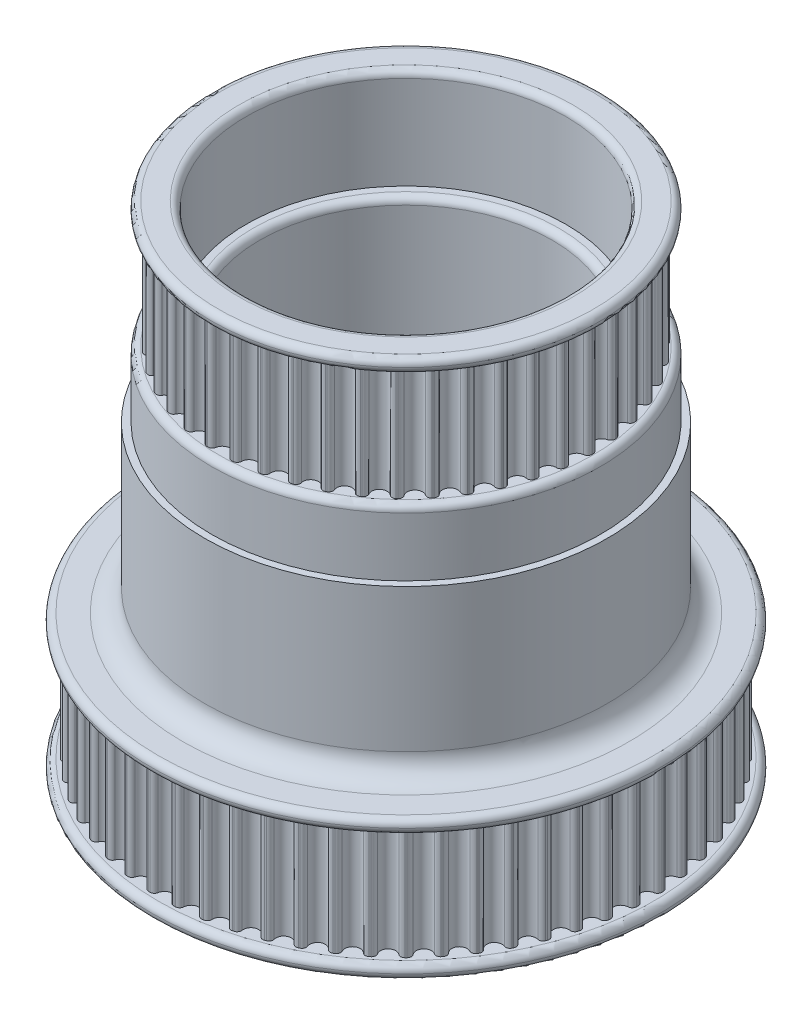
SolidWorks part; units mm, degrees
ref_plane "Front Plane" through (0, 0, 0) normal (0, 0, 1) x (1, 0, 0)
ref_plane "Top Plane" through (0, 0, 0) normal (0, 1, 0) x (1, 0, 0)
ref_plane "Right Plane" through (0, 0, 0) normal (1, 0, 0) x (0, 0, -1)
sketch "PulleyOffsets" plane through (0, 0, 0) normal (1, 0, 0) x (0, 0, -1)
  line L0 (20.6375, 0) -> (-20.6375, 0) construction
  line L1 (20.6375, 41.275) -> (-20.6375, 41.275) construction
  line L2 (0, 0) -> (0, 41.275) construction
  point P7 (0, 0)
  dimension "D1" = 41.275
ref_axis "Axis1" through (0, 34.9332, 0) along (0, -1, 0)
ref_plane "Big Pulley Plane" through (0, 0, 0) normal (0, 1, 0) x (1, 0, 0)
ref_plane "Small Pulley Plane" through (0, 41.275, 0) normal (0, 1, 0) x (1, 0, 0)
sketch "Sketch1" plane through (0, 0, 0) normal (0, 1, 0) x (1, 0, 0)
  line L0 (0, 0) -> (0, 28.2667) construction
  line L1 (0, 0) -> (2.9202, 27.7837) construction
  circle A0 centre (0, 0) radius 28.2667 construction
  circle A1 centre (0, 0) radius 27.0467 construction
  circle A2 centre (0, 27.9367) radius 0.89 construction
  circle A5 centre (2.9202, 27.7837) radius 0.89 construction
  arc A6 (0, 27.0467) -> (0.8804, 27.8061) centre (0, 27.9367) ccw
  arc A7 (0.8804, 27.8061) -> (1.3997, 28.2321) centre (1.3749, 27.7327) cw
  arc A8 (1.559, 28.2237) -> (2.031, 27.7458) centre (1.5314, 27.7245) cw
  arc A9 (2.8272, 26.8986) -> (2.031, 27.7458) centre (2.9202, 27.7837) cw
  arc A10 (1.3997, 28.2321) -> (1.559, 28.2237) centre (0, 0) cw
  arc A11 (0, 27.0467) -> (2.8272, 26.8986) centre (0, 0) ccw
  dimension "D1" = 56.5335
  dimension "D3" = 1.78
  dimension "D4" = 0.5
  dimension "D2" = 1.22
  dimension "D5" = 6
extrude "Boss-Extrude1" add sketch "Sketch1" along normal mid plane 13 contours A6 A11 A9 A8 A7 region at (0.001, 0, -0.0192)
pattern_circular "CirPattern1" count 60 over 360 about axis through (0, 34.9332, 0) along (0, -1, 0) of "Boss-Extrude1"
sketch "Sketch2" plane through (0, 0, 0) normal (1, 0, 0) x (0, 0, -1)
  line L10 (0, 6.5) -> (29.4415, 6.5) construction
  line L11 (0, 6.5) -> (0, 8.0875) construction
  line L12 (0, 8.0875) -> (29.4415, 8.0875) construction
  line L15 (29.4415, 6.5) -> (29.4415, 8.0875) construction
  line L20 (0, 34.9332) -> (0, -6.9932) construction
  line L22 (29.4415, 8.0875) -> (0, 8.0875)
  line L23 (29.4415, 8.0875) -> (29.4415, 6.5)
  line L24 (29.4415, 6.5) -> (0, 6.5)
  line L25 (0, 8.0875) -> (0, 6.5)
  dimension "D1" = 1.5875
  dimension "D2" = 29.4415
  dimension "D3" = 6.5
revolve "Revolve3" add sketch "Sketch2" angle 360 about axis through (0, 34.9332, 0) along (0, -1, 0) region at (0, 7.2937, -14.7207)
mirror "Mirror1" about plane through (0, 0, 0) normal (0, 1, 0) of "Revolve3"
sketch "Sketch6" plane through (0, 0, 0) normal (0, 1, 0) x (1, 0, 0)
  line L0 (0, 0) -> (0, 21.582) construction
  line L1 (0, 0) -> (2.8938, 21.0541) construction
  circle A0 centre (0, 0) radius 21.582 construction
  circle A1 centre (0, 0) radius 20.362 construction
  circle A2 centre (0, 21.252) radius 0.89 construction
  circle A5 centre (2.8938, 21.0541) radius 0.89 construction
  arc A6 (0, 20.362) -> (0.8793, 21.1145) centre (0, 21.252) ccw
  arc A7 (0.8793, 21.1145) -> (1.4059, 21.5362) centre (1.3733, 21.0373) cw
  arc A8 (1.5397, 21.527) -> (2.004, 21.0376) centre (1.5041, 21.0283) cw
  arc A9 (2.7726, 20.1724) -> (2.004, 21.0376) centre (2.8938, 21.0541) cw
  arc A10 (1.4059, 21.5362) -> (1.5397, 21.527) centre (0, 0) cw construction
  arc A11 (0, 20.362) -> (2.7726, 20.1724) centre (0, 0) ccw
  arc A12 (1.4059, 21.5362) -> (1.5397, 21.527) centre (0, 0) cw
  dimension "D3" = 1.78
  dimension "D4" = 0.5
  dimension "D2" = 1.22
  dimension "D1" = 43.1641
  dimension "D5" = 7.826
extrude "Boss-Extrude2" add sketch "Sketch6" along normal mid plane 13 from surface contours A6 A11 A9 A8 A7 region at (0.0017, 0, -0.025) starting at plane "Small Pulley Plane"
pattern_circular "CirPattern2" count 46 over 360 about axis through (0, 34.9332, 0) along (0, -1, 0) of "Boss-Extrude2"
sketch "Sketch9" plane through (0, 0, 0) normal (1, 0, 0) x (0, 0, -1)
  line L1 (0, 34.775) -> (22.7568, 34.775)
  line L2 (0, 34.775) -> (0, 33.1875)
  line L3 (0, 33.1875) -> (22.7568, 33.1875)
  line L4 (22.7568, 34.775) -> (22.7568, 33.1875)
  line L6 (0, 47.775) -> (22.7568, 47.775)
  line L7 (0, 47.775) -> (0, 49.3625)
  line L8 (0, 49.3625) -> (22.7568, 49.3625)
  line L9 (22.7568, 47.775) -> (22.7568, 49.3625)
  line L10 (29.4415, 8.0875) -> (29.4415, 6.5) construction
  line L11 (0, 34.9332) -> (0, -6.9932) construction
  line L12 (21.1145, 47.775) -> (20.362, 47.775) construction
  line L13 (20.1641, 34.775) -> (21.0376, 34.775) construction
  dimension "D1" = 22.7568
revolve "Revolve4" add sketch "Sketch9" angle 360 about axis through (0, 34.9332, 0) along (0, -1, 0)
sketch "Sketch10" plane through (0, -8.0875, 0) normal (0, -1, 0) x (1, 0, 0)
  circle A0 centre (0, 0) radius 18.5
  dimension "D1" = 37
extrude "Cut-Extrude1" cut sketch "Sketch10" against normal through all
sketch "Sketch11" plane through (0, 49.3625, 0) normal (0, 1, 0) x (1, 0, 0)
  circle A0 centre (0, 0) radius 22.5
  dimension "D1" = 45
extrude "Cut-Extrude2" cut sketch "Sketch11" against normal up to surface (16.175 mm away) flip side to cut up to face at (0, 33.1875, 18.5)
sketch "Sketch12" plane through (0, 0, 0) normal (0, 0, 1) x (1, 0, 0)
  line L0 (29.4415, 8.0875) -> (-29.4415, 8.0875) construction
  line L1 (18.5, 33.1875) -> (22.5, 33.1875)
  line L2 (18.5, 33.1875) -> (18.5, 8.0875) construction
  line L3 (18.5, 8.0875) -> (22.5, 8.0875)
  line L4 (22.5, 33.1875) -> (22.5, 8.0875) construction
  line L5 (22.5, 33.1875) -> (22.5, 34.775) construction
  line L6 (22.5, 27.1875) -> (22.5, 33.1875)
  line L7 (22.5, 27.1875) -> (23.2938, 27.1875)
  line L8 (22.5, 27.1875) -> (22.5, 8.0875) construction
  line L9 (22.5, 8.0875) -> (23.2938, 8.0875)
  line L10 (23.2938, 27.1875) -> (23.2938, 8.0875)
  line L11 (18.5, -8.0875) -> (18.5, 8.0875) construction
  line L12 (18.5, -1.0875) -> (16.9125, -1.0875)
  line L13 (18.5, -1.0875) -> (18.5, 37.775) construction
  line L14 (18.5, 37.775) -> (16.9125, 37.775)
  line L15 (16.9125, -1.0875) -> (16.9125, 37.775)
  line L16 (-29.4415, -8.0875) -> (29.4415, -8.0875) construction
  line L18 (18.5, -1.0875) -> (18.5, 8.0875)
  line L19 (18.5, 33.1875) -> (18.5, 37.775)
  line L20 (32.3856, 41.275) -> (-32.3856, 41.275) construction
  dimension "D1" = 6
  dimension "D2" = 0.7937
  dimension "D3" = 7
  dimension "D4" = 3.5
  dimension "D5" = 1.5875
revolve "Revolve5" add sketch "Sketch12" angle 360 about axis through (0, 34.9332, 0) along (0, -1, 0)
fillet "Fillet1" radius 2.54 1 edges at (0, 8.0875, -23.2938)
fillet "Fillet2" radius 0.7937 11 edges at (0, 37.775, 16.9125) (0, 49.3625, -18.5) (0, -8.0875, -18.5) (0, -1.0875, 16.9125) (0, -8.0875, 29.4415) (0, 8.0875, 29.4415) (0, 49.3625, 22.5) (0, 47.775, 22.5) (0, 34.775, -22.5) (0, 6.5, 29.4415) (0, -6.5, 29.4415)
equation "\"TEETH_NUM\"= 60"
equation "\"TOOTH_PITCH\"= 3mm"
equation "\"PITCH_LINE_OFFSET\"= .015in"
equation "\"DIAMETER_PER_GROOVE\"= \"OUTSIDE_DIAMETER\" / \"TEETH_NUM\" * 1in"
equation "\"PITCH_DIAMETER\"= ( ( \"TEETH_NUM\" * 3 - 1.31 ) / 3.1415 + .415 ) * 1mm"
equation "\"OUTSIDE_DIAMETER\"= \"PITCH_DIAMETER\" - \"PITCH_LINE_OFFSET\" * 2"
equation "\"D1@Sketch1\"=\"OUTSIDE_DIAMETER\""
equation "\"TOOTH_HEIGHT\"= 1.22mm"
equation "\"D2@Sketch1\"=\"TOOTH_HEIGHT\""
equation "\"TOOTH_DIAMETER\"= 1.78mm"
equation "\"INTERNAL_RADIUS\"= .5mm"
equation "\"D3@Sketch1\"=\"TOOTH_DIAMETER\""
equation "\"D5@Sketch1\"=360 / \"TEETH_NUM\""
equation "\"D4@Sketch1\"=\"INTERNAL_RADIUS\""
equation "\"D1@CirPattern1\"=\"TEETH_NUM\""
equation "\"BELT_GAP\"= 13mm"
equation "\"D2@Sketch2\"=\"PITCH_DIAMETER\"/2+1/32"
equation "\"D3@Sketch2\"=\"BELT_GAP\"/2"
equation "\"2_TEETH_NUM\"= 46"
equation "\"2_PITCH_DIAMETER\"= ( ( \"2_TEETH_NUM\" * 3 - 1.31 ) / 3.1415 + .415 ) * 1mm"
equation "\"2_OUTSIDE_DIAMETER\"= \"2_PITCH_DIAMETER\" - \"PITCH_LINE_OFFSET\" * 2"
equation "\"2_DIAMETER_PER_GROOVE\"= \"2_OUTSIDE_DIAMETER\" / \"2_TEETH_NUM\" * 1in"
equation "\"D5@Sketch6\"=360/\"2_TEETH_NUM\""
equation "\"D1@Sketch6\"=\"2_OUTSIDE_DIAMETER\""
equation "\"D2@Sketch6\"=\"TOOTH_HEIGHT\""
equation "\"D3@Sketch6\"=\"TOOTH_DIAMETER\""
equation "\"D4@Sketch6\"=\"INTERNAL_RADIUS\""
equation "\"2_BELT_GAP\"= 13mm"
equation "\"D1@CirPattern2\"=\"2_TEETH_NUM\""
equation "\"D1@Boss-Extrude2\"=\"2_BELT_GAP\""
equation "\"Pulley_OffSets\"= 1.625"
equation "\"D1@PulleyOffsets\" = \"Pulley_OffSets\""
equation "\"D1@Boss-Extrude1\"=\"BELT_GAP\""
equation "\"D1@Sketch9\"=\"2_PITCH_DIAMETER\"/2+1/32"
